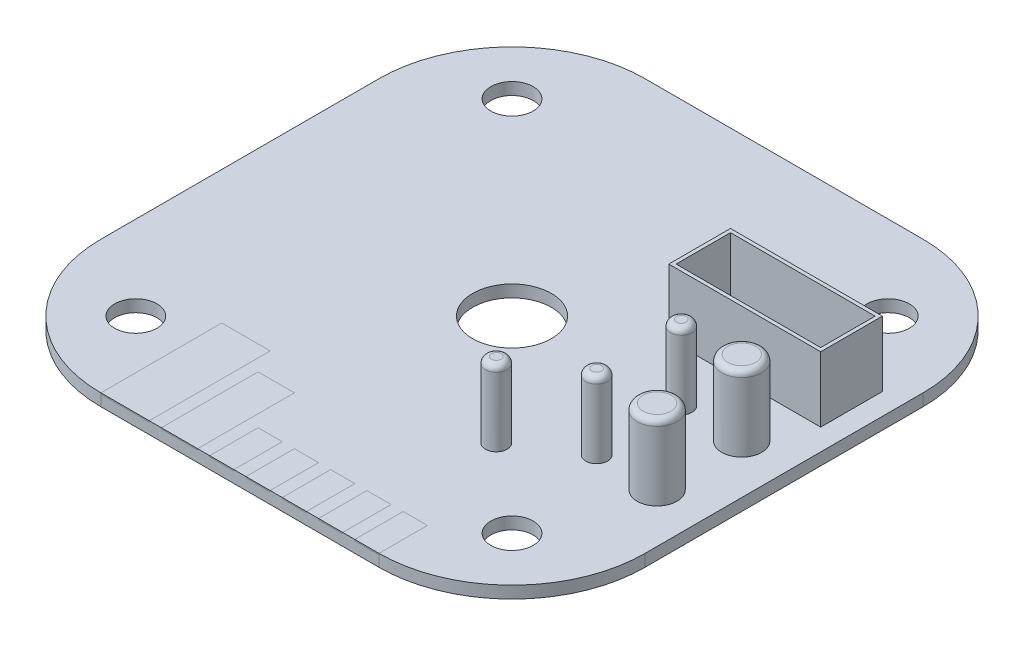
SolidWorks part; units mm, degrees
ref_plane "Front Plane" through (0, 0, 0) normal (0, 0, 1) x (1, 0, 0)
ref_plane "Top Plane" through (0, 0, 0) normal (0, 1, 0) x (1, 0, 0)
ref_plane "Right Plane" through (0, 0, 0) normal (1, 0, 0) x (0, 0, -1)
sketch "Sketch1" plane through (0, 0, 0) normal (0, 1, 0) x (1, 0, 0)
  line L1 (-22.5, -22.5) -> (22.5, -22.5)
  line L2 (-22.5, -22.5) -> (-22.5, 22.5)
  line L3 (-22.5, 22.5) -> (22.5, 22.5)
  line L4 (22.5, -22.5) -> (22.5, 22.5)
  line L5 (-22.5, -22.5) -> (22.5, 22.5) construction
  line L6 (-22.5, 22.5) -> (22.5, -22.5) construction
  point P0 (0, 0)
  dimension "D1" = 45
extrude "Boss-Extrude1" add sketch "Sketch1" along normal mid plane 1
sketch "Sketch3" plane through (0, 0, 0) normal (0, 1, 0) x (1, 0, 0)
  circle A0 centre (0, 0) radius 3.25
  dimension "D1" = 6.5
extrude "Cut-Extrude1" cut sketch "Sketch3" against normal through all both and the other way through all
fillet "Fillet1" radius 11 4 edges at (22.5, 0, 22.5) (-22.5, 0, 22.5) (-22.5, 0, -22.5) (22.5, 0, -22.5)
sketch "Sketch5" plane through (0, 0, 0) normal (0, 1, 0) x (1, 0, 0)
  line L0 (-15.5563, -15.5563) -> (15.5563, 15.5563) construction
  line L1 (-15.5563, 15.5563) -> (15.5563, -15.5563) construction
  line L2 (0, 0) -> (0, 22) construction
  circle A0 centre (0, 0) radius 22 construction
  circle A1 centre (-15.5563, 15.5563) radius 1.75
  circle A2 centre (15.5563, 15.5563) radius 1.75
  circle A3 centre (15.5563, -15.5563) radius 1.75
  circle A4 centre (-15.5563, -15.5563) radius 1.75
  point P6 (0, 0)
  point P9 (0, 0)
  dimension "D2" = 3.5
  dimension "D3" = 44
  dimension "D1" = 45
extrude "Cut-Extrude2" cut sketch "Sketch5" against normal through all both and the other way through all
sketch "Sketch6" plane through (0, 0.5, 0) normal (0, 1, 0) x (1, 0, 0)
  line L1 (8.1637, 4.8063) -> (20.7237, 4.8063)
  line L2 (8.1637, 4.8063) -> (8.1637, 9.9063)
  line L3 (8.1637, 9.9063) -> (20.7237, 9.9063)
  line L4 (20.7237, 4.8063) -> (20.7237, 9.9063)
  line L5 (8.1637, 4.8063) -> (20.7237, 9.9063) construction
  line L6 (8.1637, 9.9063) -> (20.7237, 4.8063) construction
  circle A0 centre (-15.5563, 15.5563) radius 1.75 construction
  circle A1 centre (15.5563, 15.5563) radius 1.75 construction
  point P0 (14.4437, 7.3563)
  dimension "D3" = 30
  dimension "D4" = 8.2
  dimension "D1" = 12.56
  dimension "D2" = 5.1
extrude "Extrude-Thin1" add sketch "Sketch6" along normal blind 5.4 thin thin type one direction reverse wall 0.3
sketch "Sketch7" plane through (0, 0.5, 0) normal (0, 1, 0) x (1, 0, 0)
  line L0 (20.4237, 5.1063) -> (20.4237, 9.6063) construction
  line L1 (8.4637, 5.1063) -> (20.4237, 5.1063) construction
  line L2 (8.4637, 9.6063) -> (8.4637, 5.1063) construction
  line L3 (20.4237, 9.6063) -> (8.4637, 9.6063) construction
  line L4 (20.4237, 5.1063) -> (20.4237, 9.6063)
  line L5 (8.4637, 5.1063) -> (20.4237, 5.1063)
  line L6 (8.4637, 9.6063) -> (8.4637, 5.1063)
  line L7 (20.4237, 9.6063) -> (8.4637, 9.6063)
extrude "Boss-Extrude2" add sketch "Sketch7" along normal blind 0.3
sketch "Sketch8" plane through (0, 0.5, 0) normal (0, 1, 0) x (1, 0, 0)
  line L0 (-11.5, -22.5) -> (11.5, -22.5) construction
  line L1 (-2.5, -22.5) -> (-0.5, -22.5)
  line L2 (-2.5, -22.5) -> (-2.5, -18.5)
  line L3 (-2.5, -18.5) -> (-0.5, -18.5)
  line L4 (-0.5, -22.5) -> (-0.5, -18.5)
  line L5 (-0.5, -18.5) -> (0.5, -18.5) construction
  line L6 (0.5, -22.5) -> (2.5, -22.5)
  line L7 (0.5, -22.5) -> (0.5, -18.5)
  line L8 (0.5, -18.5) -> (2.5, -18.5)
  line L9 (2.5, -22.5) -> (2.5, -18.5)
  line L10 (3.5, -22.5) -> (5.5, -22.5)
  line L11 (3.5, -22.5) -> (3.5, -18.5)
  line L12 (3.5, -18.5) -> (5.5, -18.5)
  line L13 (5.5, -22.5) -> (5.5, -18.5)
  line L14 (6.5, -22.5) -> (8.5, -22.5)
  line L15 (6.5, -22.5) -> (6.5, -18.5)
  line L16 (6.5, -18.5) -> (8.5, -18.5)
  line L17 (8.5, -22.5) -> (8.5, -18.5)
  line L18 (9.5, -22.5) -> (11.5, -22.5)
  line L19 (9.5, -22.5) -> (9.5, -18.5)
  line L20 (9.5, -18.5) -> (11.5, -18.5)
  line L21 (11.5, -22.5) -> (11.5, -18.5)
  line L22 (2.5, -18.5) -> (3.5, -18.5) construction
  line L23 (5.5, -18.5) -> (6.5, -18.5) construction
  line L24 (8.5, -18.5) -> (9.5, -18.5) construction
  line L26 (-11.5, -22.5) -> (-7.5, -22.5)
  line L27 (-11.5, -22.5) -> (-11.5, -12.5)
  line L28 (-11.5, -12.5) -> (-7.5, -12.5)
  line L29 (-7.5, -22.5) -> (-7.5, -12.5)
  line L30 (-6.5, -22.5) -> (-3.5, -22.5)
  line L31 (-6.5, -22.5) -> (-6.5, -14.5)
  line L32 (-6.5, -14.5) -> (-3.5, -14.5)
  line L33 (-3.5, -22.5) -> (-3.5, -14.5)
  dimension "D1" = 2
  dimension "D2" = 1
  dimension "D3" = 4
  dimension "D4" = 10
  dimension "D5" = 4
  dimension "D6" = 1
  dimension "D7" = 3
  dimension "D8" = 8
  dimension "D9" = 1
extrude "Cut-Extrude3" cut sketch "Sketch8" against normal blind 0.1
sketch "Sketch9" plane through (0, 0.4, 0) normal (0, 1, 0) x (1, 0, 0)
  line L0 (9.5, -18.5) -> (9.5, -22.5) construction
  line L1 (9.5, -22.5) -> (11.5, -22.5) construction
  line L2 (11.5, -22.5) -> (11.5, -18.5) construction
  line L3 (11.5, -18.5) -> (9.5, -18.5) construction
  line L4 (6.5, -18.5) -> (6.5, -22.5) construction
  line L5 (6.5, -22.5) -> (8.5, -22.5) construction
  line L6 (8.5, -22.5) -> (8.5, -18.5) construction
  line L7 (8.5, -18.5) -> (6.5, -18.5) construction
  line L8 (3.5, -18.5) -> (3.5, -22.5) construction
  line L9 (3.5, -22.5) -> (5.5, -22.5) construction
  line L10 (5.5, -22.5) -> (5.5, -18.5) construction
  line L11 (5.5, -18.5) -> (3.5, -18.5) construction
  line L12 (0.5, -18.5) -> (0.5, -22.5) construction
  line L13 (0.5, -22.5) -> (2.5, -22.5) construction
  line L14 (2.5, -22.5) -> (2.5, -18.5) construction
  line L15 (2.5, -18.5) -> (0.5, -18.5) construction
  line L16 (-2.5, -18.5) -> (-2.5, -22.5) construction
  line L17 (-2.5, -22.5) -> (-0.5, -22.5) construction
  line L18 (-0.5, -22.5) -> (-0.5, -18.5) construction
  line L19 (-0.5, -18.5) -> (-2.5, -18.5) construction
  line L20 (-6.5, -14.5) -> (-6.5, -22.5) construction
  line L21 (-6.5, -22.5) -> (-3.5, -22.5) construction
  line L22 (-3.5, -22.5) -> (-3.5, -14.5) construction
  line L23 (-3.5, -14.5) -> (-6.5, -14.5) construction
  line L24 (-11.5, -12.5) -> (-11.5, -22.5) construction
  line L25 (-11.5, -22.5) -> (-7.5, -22.5) construction
  line L26 (-7.5, -22.5) -> (-7.5, -12.5) construction
  line L27 (-7.5, -12.5) -> (-11.5, -12.5) construction
  line L28 (9.5, -18.5) -> (9.5, -22.5)
  line L29 (9.5, -22.5) -> (11.5, -22.5)
  line L30 (11.5, -22.5) -> (11.5, -18.5)
  line L31 (11.5, -18.5) -> (9.5, -18.5)
  line L32 (6.5, -18.5) -> (6.5, -22.5)
  line L33 (6.5, -22.5) -> (8.5, -22.5)
  line L34 (8.5, -22.5) -> (8.5, -18.5)
  line L35 (8.5, -18.5) -> (6.5, -18.5)
  line L36 (3.5, -18.5) -> (3.5, -22.5)
  line L37 (3.5, -22.5) -> (5.5, -22.5)
  line L38 (5.5, -22.5) -> (5.5, -18.5)
  line L39 (5.5, -18.5) -> (3.5, -18.5)
  line L40 (0.5, -18.5) -> (0.5, -22.5)
  line L41 (0.5, -22.5) -> (2.5, -22.5)
  line L42 (2.5, -22.5) -> (2.5, -18.5)
  line L43 (2.5, -18.5) -> (0.5, -18.5)
  line L44 (-2.5, -18.5) -> (-2.5, -22.5)
  line L45 (-2.5, -22.5) -> (-0.5, -22.5)
  line L46 (-0.5, -22.5) -> (-0.5, -18.5)
  line L47 (-0.5, -18.5) -> (-2.5, -18.5)
  line L48 (-6.5, -14.5) -> (-6.5, -22.5)
  line L49 (-6.5, -22.5) -> (-3.5, -22.5)
  line L50 (-3.5, -22.5) -> (-3.5, -14.5)
  line L51 (-3.5, -14.5) -> (-6.5, -14.5)
  line L52 (-11.5, -12.5) -> (-11.5, -22.5)
  line L53 (-11.5, -22.5) -> (-7.5, -22.5)
  line L54 (-7.5, -22.5) -> (-7.5, -12.5)
  line L55 (-7.5, -12.5) -> (-11.5, -12.5)
extrude "Boss-Extrude3" add sketch "Sketch9" along normal up to surface (0.1 mm away) separate body up to face at (-15.5563, 0.5, 17.3063)
sketch "Sketch10" plane through (0, 0.5, 0) normal (0, 1, 0) x (1, 0, 0)
  line L0 (13.4437, 0.5563) -> (13.4437, -6.4437) construction
  line L1 (18.4437, 0.5563) -> (18.4437, -6.4437) construction
  line L2 (13.4437, -2.9437) -> (18.4437, -2.9437) construction
  circle A0 centre (18.4437, 0.5563) radius 1.65
  circle A1 centre (18.4437, -6.4437) radius 1.65
  circle A2 centre (13.4437, -6.4437) radius 0.9
  circle A3 centre (13.4437, 0.5563) radius 0.9
  circle A4 centre (8.4437, -9.7437) radius 0.9
  circle A5 centre (-15.5563, 15.5563) radius 1.75 construction
  dimension "D1" = 1.8
  dimension "D2" = 3.3
  dimension "D3" = 34
  dimension "D4" = 15
  dimension "D5" = 22
  dimension "D6" = 24
  dimension "D7" = 29
  dimension "D8" = 25.3
extrude "Boss-Extrude4" add sketch "Sketch10" along normal blind 6.2
fillet "Fillet2" radius 0.5 5 edges at (18.4437, 6.7, 8.0937) (18.4437, 6.7, 1.0937) (13.4437, 6.7, 0.3437) (13.4437, 6.7, 7.3437) (8.4437, 6.7, 10.6437)
